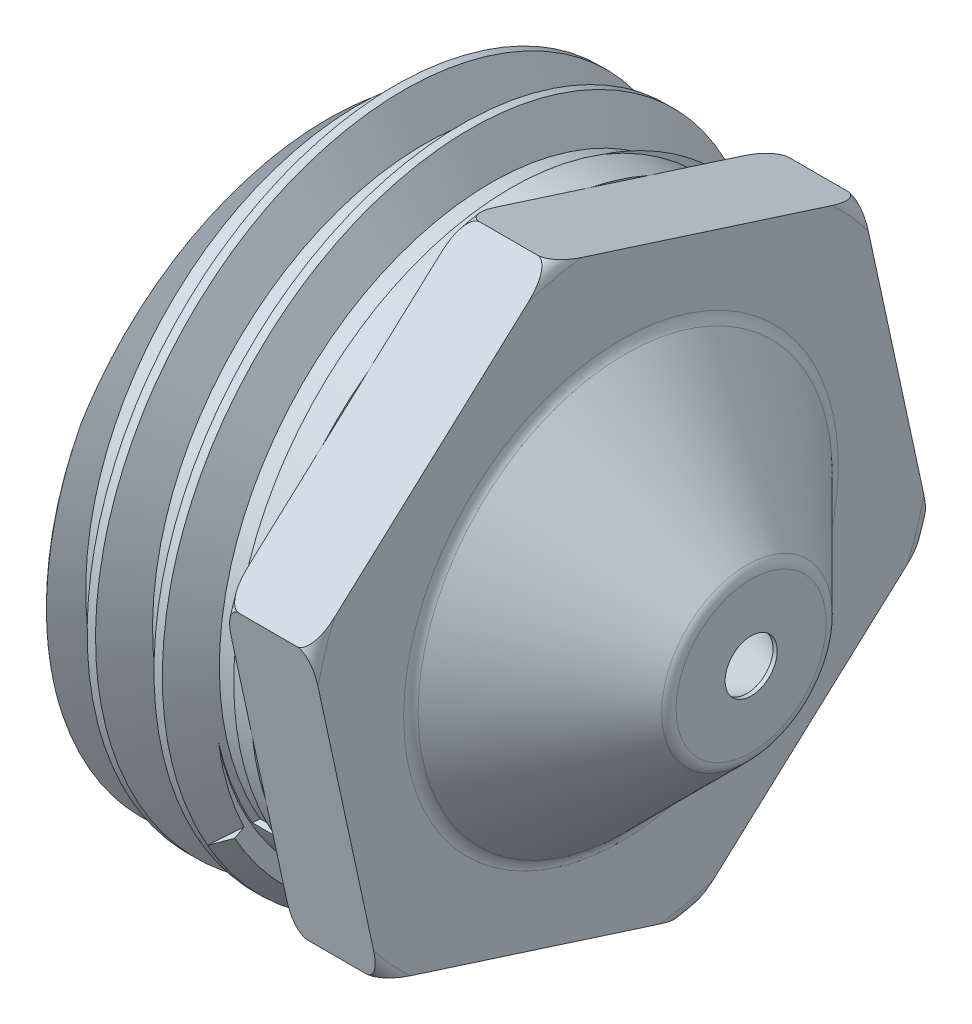
SolidWorks part; units mm, degrees
material "AISI Acero para herramientas tipo A2"
ref_plane "Alzado" through (0, 0, 0) normal (0, 0, 1) x (1, 0, 0)
ref_plane "Planta" through (0, 0, 0) normal (0, 1, 0) x (1, 0, 0)
ref_plane "Vista lateral" through (0, 0, 0) normal (1, 0, 0) x (0, 0, -1)
sketch "Sketch1" plane through (0, 0, 0) normal (0, 0, 1) x (1, 0, 0)
  line L0 (-1000, 0) -> (49000, 0) construction
  line L1 (14, 0) -> (14, 2.8026)
  line L2 (14, 2.8026) -> (9.5, 7.3026)
  line L3 (9.5, 7.3026) -> (9.5, 11.2355)
  line L4 (9.5, 11.2355) -> (6.5, 11.2355)
  line L5 (6.5, 11.2355) -> (6.5, 9.7882)
  line L6 (6.5, 9.7882) -> (5.1959, 9.7882)
  line L7 (5.1959, 9.7882) -> (5.1959, 10.8534)
  line L8 (5.1959, 10.8534) -> (0, 10.8534)
  line L9 (0, 10.8534) -> (0, 0)
  line L11 (14, 0) -> (0, 0)
  dimension "D1" = 45
  dimension "D2" = 3
  dimension "D3" = 14
  dimension "D5" = 6.5
revolve "Revolve1" add sketch "Sketch1" angle 360 about L0
sketch "Sketch2" plane through (14, 0, 0) normal (1, 0, 0) x (0, 0, -1)
  circle A0 centre (0, 0) radius 0.9
  dimension "D1" = 1.8
extrude "Cut-Extrude1" cut sketch "Sketch2" against normal through all
fillet "Fillet2" radius 0.5 2 edges at (6.5, 0, 11.2355) (9.5, 0, 11.2355)
sketch "Sketch3" plane through (9.5, 0, 0) normal (1, 0, 0) x (0, 0, -1)
  line L1 (8.3182, 7.5528) -> (-2.3818, 10.9802)
  line L2 (-2.3818, 10.9802) -> (-10.7, 3.4274)
  line L3 (-10.7, 3.4274) -> (-8.3182, -7.5528)
  line L4 (-8.3182, -7.5528) -> (2.3818, -10.9802)
  line L5 (2.3818, -10.9802) -> (10.7, -3.4274)
  line L6 (10.7, -3.4274) -> (8.3182, 7.5528)
  circle A0 centre (0, 0) radius 9.7303 construction
  circle A1 centre (0, 0) radius 11.2355 construction
extrude "Cut-Extrude2" cut sketch "Sketch3" along normal through all and the other way up to surface (3 mm away) flip side to cut other way up to face at (6.5, 0, -10.7355)
fillet "Fillet3" radius 0.5 1 edges at (14, 0, 2.8026)
fillet "Fillet4" radius 0.5 1 edges at (9.5, 0, 7.3026)
chamfer "Chamfer3" distance 0.5 angle 45 2 edges at (0, 0, 10.8534) (5.1959, 0, 10.8534)
thread "Thread1" pitch 2.3091 method cut profile "Perfil de rosca1" start angle 0, offset 11, length 0, pitch 2.3091, diameter 21.7067
ref_plane "Plane1" through (-10.5, 0, -10.8534) normal (0, -1, 0) x (0, 0, -1)
sketch "Perfil de rosca1" plane through (-10.5, 0, -10.8534) normal (0, -1, 0) x (0, 0, -1)
  line L0 (0, 0) -> (0, 2.3091) construction
  line L11 (0, 0) -> (0, 2.0205)
  line L12 (0, 2.0205) -> (-1.2498, 1.2989)
  line L13 (-1.2498, 1.2989) -> (-1.2498, 0.7216)
  line L15 (-1.2498, 0.7216) -> (0, 0)
  line L17 (-1.2498, 1.0102) -> (0, 1.0102) construction
  point P2 (0, 0)
  dimension "Pitch" = 2.3091
  dimension "Profile_Angle" = 60
  dimension "Profile_Land" = 0.5773
  dimension "Profile_Height" = 1.2498
chamfer "Chamfer2" distance 8 angle 60 1 edges at (0, 0, -0.9) first distance on face at (0, 0, -0.9)
